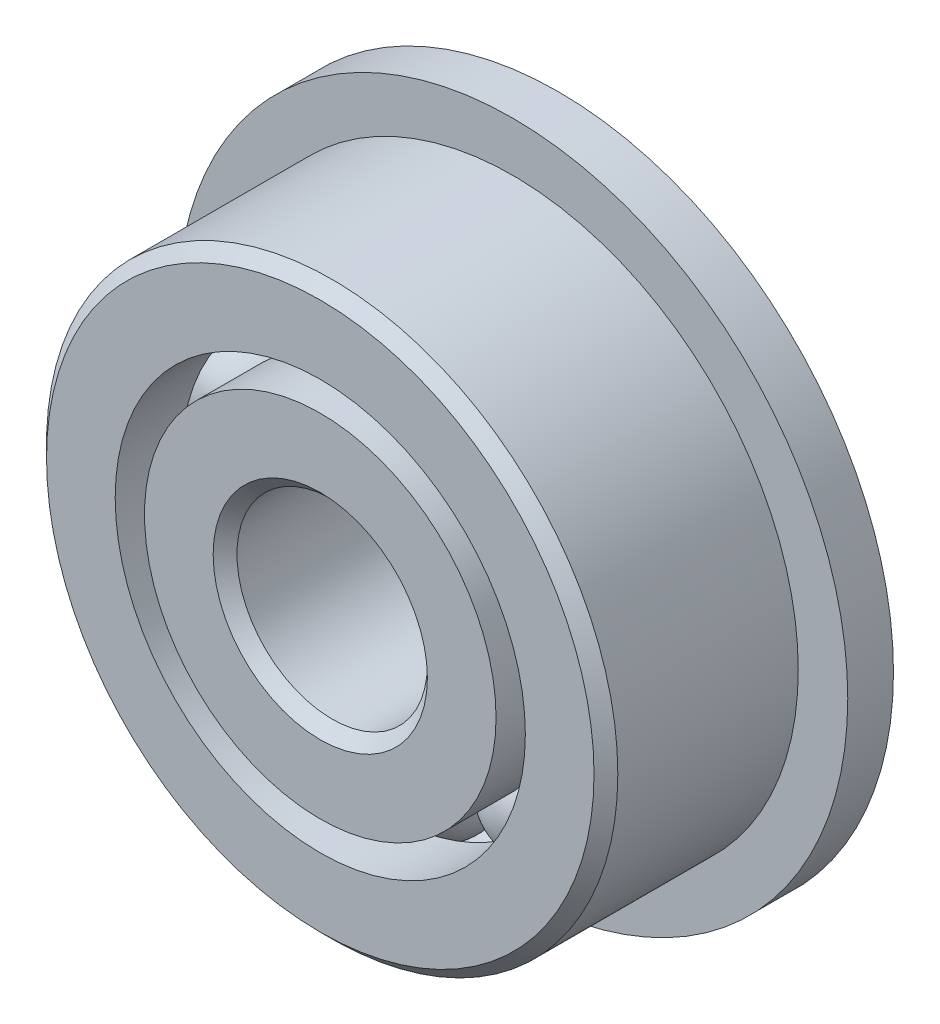
SolidWorks part; units mm, degrees
ref_plane "Front Plane" through (0, 0, 0) normal (0, 0, 1) x (1, 0, 0)
ref_plane "Top Plane" through (0, 0, 0) normal (0, 1, 0) x (1, 0, 0)
ref_plane "Right Plane" through (0, 0, 0) normal (1, 0, 0) x (0, 0, -1)
sketch "Sketch1" plane through (0, 0, 0) normal (1, 0, 0) x (0, 0, -1)
  line L0 (-1.9844, 0) -> (1.9844, 0) construction
  line L1 (0, 4.7625) -> (0, -4.7625) construction
  line L2 (1.7859, 4.7625) -> (-1.7859, 4.7625)
  line L3 (-1.7859, 4.7625) -> (-1.9844, 4.5641)
  line L4 (-1.9844, 4.5641) -> (-1.9844, 3.4192)
  line L5 (-1.9844, 3.4192) -> (-0.8819, 3.4192)
  line L6 (1.9844, 3.4192) -> (0.8819, 3.4192)
  line L7 (1.9844, 4.5641) -> (1.9844, 3.4192)
  line L8 (1.7859, 4.7625) -> (1.9844, 4.5641)
  line L9 (0, 4.7625) -> (0, 3.175) construction
  line L10 (0, 3.175) -> (0, 1.5875) construction
  arc A0 (-0.8819, 3.4192) -> (0.8819, 3.4192) centre (0, 3.175) cw
  point P14 (0, 1.5875)
  dimension "Width" = 3.9688
  dimension "OD" = 9.525
  dimension "D1" = 45
  dimension "D2" = 0.1984
  dimension "Shaft Dia" = 3.175
  dimension "D3" = 1.7639
  dimension "D4" = 0.2442
revolve "Revolve1" add sketch "Sketch1" angle 360 about L0
sketch "Sketch3" plane through (0, 0, 0) normal (1, 0, 0) x (0, 0, -1)
  line L0 (-1.9844, 2.9308) -> (-0.8819, 2.9308)
  line L1 (0, 4.7625) -> (0, -4.7625) construction
  line L2 (-1.9844, 4.5641) -> (-1.9844, 3.4192) construction
  line L3 (-1.9844, 2.9308) -> (-1.9844, 1.7859)
  line L4 (-1.7859, 4.7625) -> (-1.9844, 4.5641) construction
  line L5 (-1.9844, 1.7859) -> (-1.7859, 1.5875)
  line L6 (-1.7859, 1.5875) -> (1.7859, 1.5875)
  line L7 (1.7859, 4.7625) -> (1.7859, -4.7625) construction
  line L8 (1.7859, 1.5875) -> (1.9844, 1.7859)
  line L9 (1.9844, -4.5641) -> (1.9844, 4.5641) construction
  line L10 (1.9844, 1.7859) -> (1.9844, 2.9308)
  line L11 (1.9844, 2.9308) -> (0.8819, 2.9308)
  line L13 (1.7859, 4.7625) -> (1.9844, 4.5641) construction
  arc A0 (0.8819, 3.4192) -> (-0.8819, 3.4192) centre (0, 3.175) ccw construction
  arc A1 (0.8819, 2.9308) -> (-0.8819, 2.9308) centre (0, 3.175) cw
revolve "Revolve3" add sketch "Sketch3" angle 360 about L0
sketch "Sketch4" plane through (0, 0, 0) normal (1, 0, 0) x (0, 0, -1)
  line L0 (-0.9151, 3.175) -> (0.9151, 3.175)
  arc A2 (-0.9151, 3.175) -> (0.9151, 3.175) centre (0, 3.175) cw
  arc A3 (0.8819, 3.4192) -> (-0.8819, 3.4192) centre (0, 3.175) ccw construction
revolve "Revolve4" add sketch "Sketch4" angle 360 about L0
ref_axis "Axis1" through (0, 0, -1.9844) along (0, 0, 1)
pattern_circular "CirPattern1" count 10 every 36 about axis through (0, 0, -1.9844) along (0, 0, 1) of bodies 104
sketch "Sketch5" plane through (0, 0, 0) normal (1, 0, 0) x (0, 0, -1)
  line L0 (-1.9844, 3.4192) -> (-0.8819, 3.4192) construction
  line L1 (-1.8852, 3.4192) -> (-0.9151, 3.4192)
  line L2 (-1.8852, 3.4192) -> (-1.8852, 2.9308)
  line L3 (-1.8852, 2.9308) -> (-0.9151, 2.9308)
  line L4 (-0.9151, 3.4192) -> (-0.9151, 2.9308)
  line L5 (-1.9844, 2.9308) -> (-0.8819, 2.9308) construction
  line L6 (1.9844, 3.4192) -> (0.8819, 3.4192) construction
  line L7 (1.8852, 3.4192) -> (0.9151, 3.4192)
  line L8 (1.8852, 3.4192) -> (1.8852, 2.9308)
  line L9 (1.8852, 2.9308) -> (0.9151, 2.9308)
  line L10 (0.9151, 3.4192) -> (0.9151, 2.9308)
  line L11 (1.9844, 2.9308) -> (0.8819, 2.9308) construction
  line L12 (-1.7859, 4.7625) -> (-1.9844, 4.5641) construction
  point P18 (-1.8852, 4.6633)
revolve "Revolve5" [suppressed] add sketch "Sketch5" angle 360 about L0
sketch "Sketch6" plane through (0, 0, 0) normal (1, 0, 0) x (0, 0, -1)
  line L0 (1.9844, 0) -> (-1.9844, 0) construction
  line L1 (1.9844, 3.4192) -> (1.2224, 3.4192)
  line L2 (1.9844, 3.4192) -> (1.9844, 5.588)
  line L3 (1.9844, 5.588) -> (1.2224, 5.588)
  line L4 (1.2224, 3.4192) -> (1.2224, 5.588)
  dimension "Th" = 0.762
  dimension "Flange OD" = 11.176
revolve "Revolve6" add sketch "Sketch6" angle 360 about L0
equation "\"D2@Sketch1\" = \"Width@Sketch1\"*.05"
equation "\"D3@Sketch1\" = \"Width@Sketch1\"/2.25"
equation "\"D4@Sketch1\" = (((\"OD@Sketch1\"-\"Width@Sketch1\")/2)/3.25)/3.5"
equation "\"D2@CirPattern1\" = 360/\"Balls@CirPattern1\""
